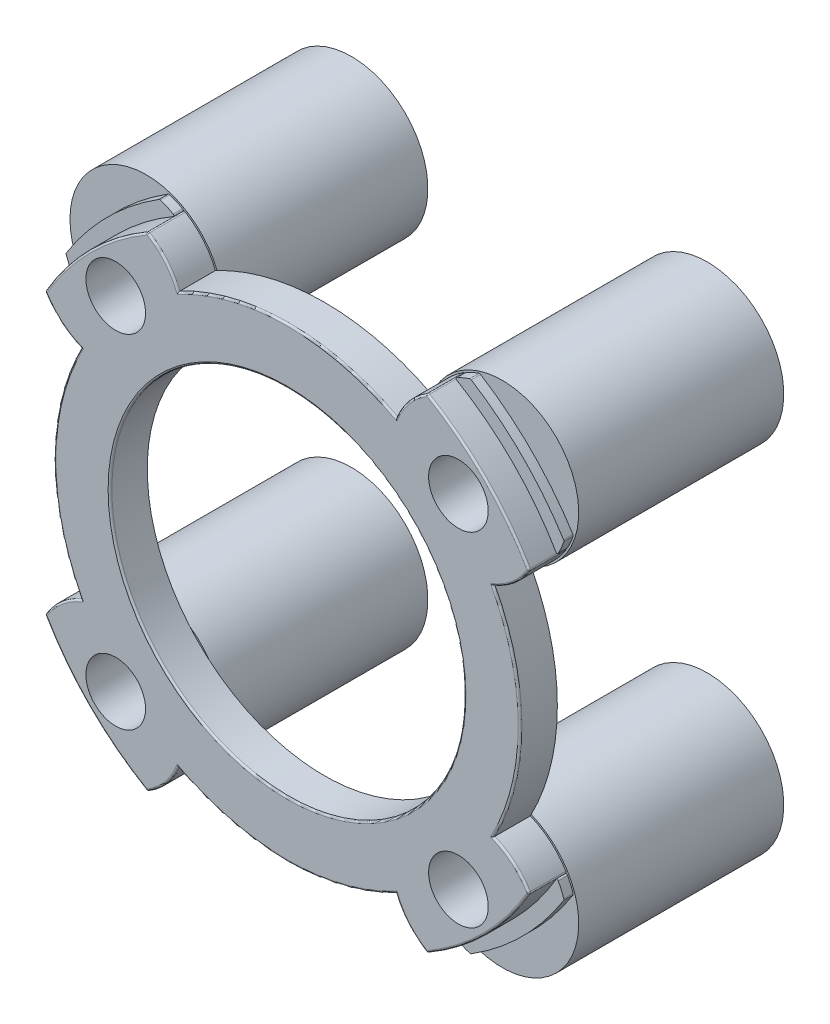
SolidWorks part; units mm, degrees
material "ABS"
ref_plane "Front Plane" through (0, 0, 0) normal (0, 0, 1) x (1, 0, 0)
ref_plane "Top Plane" through (0, 0, 0) normal (0, 1, 0) x (1, 0, 0)
ref_plane "Right Plane" through (0, 0, 0) normal (1, 0, 0) x (0, 0, -1)
ref_plane "Output Plane" through (0, 0, 15) normal (0, 0, -1) x (-1, 0, 0)
sketch "CYC Output Sketch" plane through (0, 0, 15) normal (0, 0, 1) x (1, 0, 0)
  line L1 (9.5459, 9.5459) -> (-9.5459, 9.5459) construction
  line L2 (-9.5459, 9.5459) -> (-9.5459, -9.5459) construction
  line L3 (-9.5459, -9.5459) -> (9.5459, -9.5459) construction
  line L4 (9.5459, -9.5459) -> (9.5459, 9.5459) construction
  circle A0 centre (0, 0) radius 13.5 construction
sketch "Sketch3" plane through (0, 0, 15) normal (0, 0, -1) x (-1, 0, 0)
  circle A0 centre (-9.5459, 9.5459) radius 4
  circle A1 centre (9.5459, 9.5459) radius 4
  circle A2 centre (9.5459, -9.5459) radius 4
  circle A3 centre (-9.5459, -9.5459) radius 4
  dimension "D1" = 8
extrude "Boss-Extrude1" add sketch "Sketch3" along normal blind 11
sketch "Sketch6" plane through (0, 0, 15) normal (0, 0, 1) x (1, 0, 0)
  arc A0 (-7.5062, 12.9868) -> (-12.9868, 7.5062) centre (0, 0) ccw
  arc A5 (-11.0518, 5.8402) -> (-11.0518, -5.8402) centre (0, 0) ccw
  circle A6 centre (0, 0) radius 9.5
  arc A7 (-5.8402, 11.0518) -> (-7.5062, 12.9868) centre (-9.5459, 9.5459) ccw
  arc A8 (11.0518, 5.8402) -> (12.9868, 7.5062) centre (9.5459, 9.5459) ccw
  arc A9 (5.8402, -11.0518) -> (7.5062, -12.9868) centre (9.5459, -9.5459) ccw
  arc A10 (-11.0518, -5.8402) -> (-12.9868, -7.5062) centre (-9.5459, -9.5459) ccw
  arc A11 (5.8402, 11.0518) -> (-5.8402, 11.0518) centre (0, 0) ccw
  arc A12 (11.0518, -5.8402) -> (11.0518, 5.8402) centre (0, 0) ccw
  arc A13 (-5.8402, -11.0518) -> (5.8402, -11.0518) centre (0, 0) ccw
  arc A14 (7.5062, 12.9868) -> (5.8402, 11.0518) centre (9.5459, 9.5459) ccw
  arc A15 (12.9868, -7.5062) -> (11.0518, -5.8402) centre (9.5459, -9.5459) ccw
  arc A16 (-7.5062, -12.9868) -> (-5.8402, -11.0518) centre (-9.5459, -9.5459) ccw
  arc A17 (-12.9868, 7.5062) -> (-11.0518, 5.8402) centre (-9.5459, 9.5459) ccw
  arc A18 (12.9868, 7.5062) -> (7.5062, 12.9868) centre (0, 0) ccw
  arc A19 (7.5062, -12.9868) -> (12.9868, -7.5062) centre (0, 0) ccw
  arc A20 (-12.9868, -7.5062) -> (-7.5062, -12.9868) centre (0, 0) ccw
  dimension "D2" = 30
  dimension "D3" = 25
  dimension "D4" = 8
  dimension "D1" = 19
  dimension "D5" = 27
extrude "Boss-Extrude6" add sketch "Sketch6" along normal blind 2 contours A6 | A0 A17 A5 A10 A20 A16 A13 A9 A19 A15 A12 A8 A18 A14 A11 A7
fillet "Fillet1" radius 0.1 17 edges at (9.5, 0, 17) (0, 12.5, 17) (6.5147, 12.1558, 17) (10.6066, 10.6066, 17) (12.1558, 6.5147, 17) (12.5, 0, 17) (12.1558, -6.5147, 17) (10.6066, -10.6066, 17) (6.5147, -12.1558, 17) (0, -12.5, 17) (-6.5147, -12.1558, 17) (-10.6066, -10.6066, 17) (-12.1558, -6.5147, 17) (-12.5, 0, 17) (-12.1558, 6.5147, 17) (-10.6066, 10.6066, 17) (-6.5147, 12.1558, 17)
fillet "Fillet2" radius 0.1 16 edges at (-7.5063, -12.9669, 16.9561) (-12.9669, -7.5063, 16.9561) (-12.9669, 7.5063, 16.9561) (-7.5063, 12.9669, 16.9561) (7.5063, 12.9669, 16.9561) (7.5063, -12.9669, 16.9561) (12.9669, -7.5063, 16.9561) (12.9669, 7.5063, 16.9561) (-7.5062, -12.9868, 15.95) (-12.9868, -7.5062, 15.95) (-12.9868, 7.5062, 15.95) (-7.5062, 12.9868, 15.95) (7.5062, 12.9868, 15.95) (12.9868, -7.5062, 15.95) (7.5062, -12.9868, 15.95) (12.9868, 7.5062, 15.95)
sketch "Sketch7" plane through (0, 0, 15) normal (0, 0, -1) x (-1, 0, 0)
  arc A0 (-13.3601, -8.3409) -> (-8.3409, -13.3601) centre (0, 0) ccw
  arc A1 (8.3409, 13.3601) -> (13.3601, 8.3409) centre (9.5459, 9.5459) ccw
  arc A2 (-13.3601, 8.3409) -> (-8.3409, 13.3601) centre (-9.5459, 9.5459) ccw
  arc A3 (-8.3409, -13.3601) -> (-13.3601, -8.3409) centre (-9.5459, -9.5459) ccw
  circle A4 centre (9.5459, -9.5459) radius 4
  arc A5 (-8.3409, 13.3601) -> (-13.3601, 8.3409) centre (0, 0) ccw
  arc A6 (8.3409, -13.3601) -> (13.3601, -8.3409) centre (0, 0) ccw
  arc A7 (13.3601, 8.3409) -> (8.3409, 13.3601) centre (0, 0) ccw
  arc A8 (12.9868, 7.5062) -> (7.5062, 12.9868) centre (0, 0) ccw
  arc A9 (-7.5062, 12.9868) -> (-12.9868, 7.5062) centre (0, 0) ccw
  arc A10 (-12.9868, -7.5062) -> (-7.5062, -12.9868) centre (0, 0) ccw
  arc A11 (7.5062, -12.9868) -> (12.9868, -7.5062) centre (0, 0) ccw
  dimension "D1" = 31.5
  dimension "D2" = 8
  dimension "D3" = 30
extrude "Boss-Extrude7" add sketch "Sketch7" against normal blind 0.5 contours A8 A1 A7 | A9 A2 A5 | A10 A3 A0 | A11 A4 A6
fillet "Fillet3" radius 0.1 16 edges at (-8.3409, -13.3601, 15.25) (-13.3601, -8.3409, 15.25) (-7.5062, -12.9868, 15.25) (-12.9868, -7.5062, 15.25) (-13.3601, 8.3409, 15.25) (-8.3409, 13.3601, 15.25) (-12.9868, 7.5062, 15.25) (-7.5062, 12.9868, 15.25) (8.3409, 13.3601, 15.25) (13.3601, 8.3409, 15.25) (7.5062, 12.9868, 15.25) (12.9868, 7.5062, 15.25) (13.3601, -8.3409, 15.25) (8.3409, -13.3601, 15.25) (12.9868, -7.5062, 15.25) (7.5062, -12.9868, 15.25)
sketch "Sketch8" plane through (0, 0, 17) normal (0, 0, 1) x (1, 0, 0)
  line L0 (0, 0) -> (9.1924, 9.1924) construction
  line L1 (0, 0) -> (13, 0) construction
  circle A0 centre (0, 0) radius 13 construction
  circle A1 centre (9.1924, 9.1924) radius 1.6
  circle A2 centre (9.1924, -9.1924) radius 1.6
  circle A3 centre (-9.1924, -9.1924) radius 1.6
  circle A4 centre (-9.1924, 9.1924) radius 1.6
  point P16 (0, 0)
  dimension "D1" = 26
  dimension "D2" = 45
  dimension "D3" = 3.2
  dimension "D4" = 4
extrude "Cut-Extrude1" cut sketch "Sketch8" against normal through all
sketch "Sketch9" plane through (0, 0, 17) normal (0, 0, 1) x (1, 0, 0)
  circle A0 centre (9.1924, 9.1924) radius 2.75
  circle A1 centre (9.1924, -9.1924) radius 2.75
  circle A2 centre (-9.1924, -9.1924) radius 2.75
  circle A3 centre (-9.1924, 9.1924) radius 2.75
  point P12 (0, 0)
  dimension "D1" = 5.5
  dimension "D2" = 4
extrude "Cut-Extrude2" cut sketch "Sketch9" along normal blind 3 from surface at -13 starting at face at (10.7924, 9.1924, 4)
sketch "Sketch10" plane through (0, 0, 4) normal (0, 0, -1) x (-1, 0, 0)
  circle A0 centre (9.5459, 9.5459) radius 4.1
  circle A1 centre (9.5459, 9.5459) radius 4
  circle A2 centre (9.5459, -9.5459) radius 4
  circle A3 centre (9.5459, -9.5459) radius 4.1
  circle A4 centre (-9.5459, -9.5459) radius 4
  circle A5 centre (-9.5459, -9.5459) radius 4.1
  circle A6 centre (-9.5459, 9.5459) radius 4
  circle A7 centre (-9.5459, 9.5459) radius 4.1
  point P4 (0.6151, -0.4012)
  point P5 (0, 0)
  point P16 (0, 0)
  dimension "D1" = 8
  dimension "D2" = 8.2
  dimension "D3" = 4
extrude "Boss-Extrude8" add sketch "Sketch10" against normal blind 11
equation "\"RingPinShaft\"= 5.05"
equation "\"CenterBearingOut\"=32.05"
equation "\"RingPostIn\"=5.15"
equation "\"CamBearingOut\"=15.1"
equation "\"DiskOutputShaft\"=10.1"
equation "\"CenterShaft\"=25.2"
equation "\"Eccentricity\"=2"
equation "\"CycCamShaft\"=10.05"
equation "\"D2@Sketch6\"=\"OutputBearing\""
equation "\"OutputBearing\"=30"
